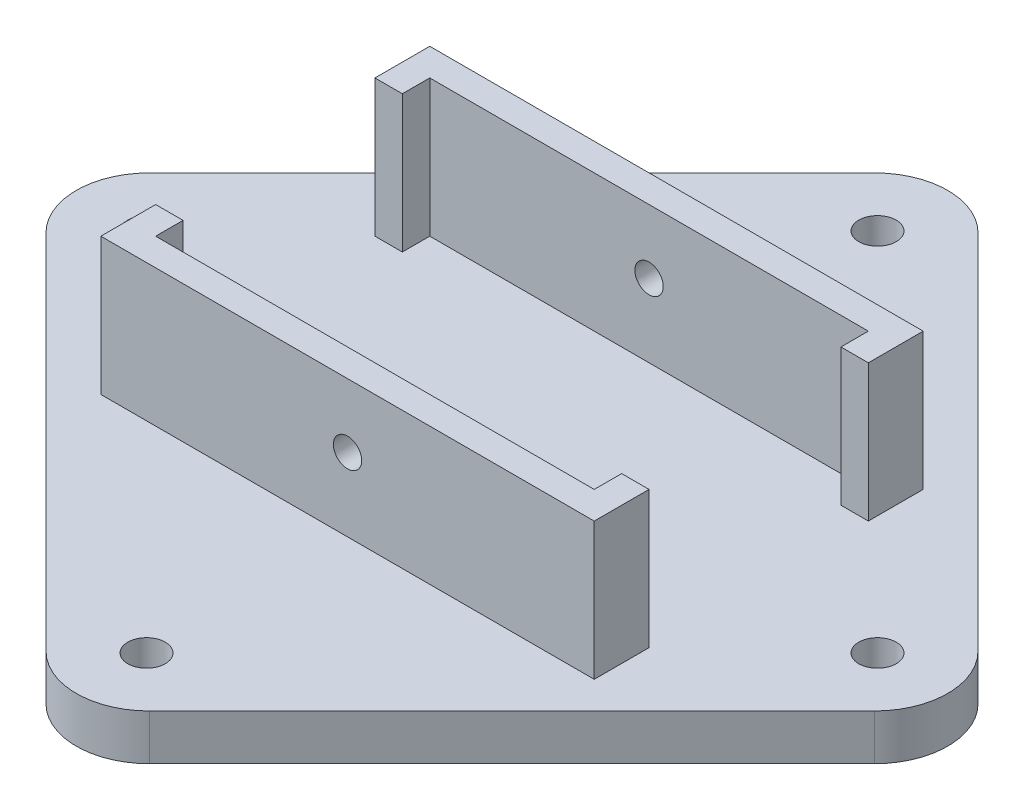
SolidWorks part; units mm, degrees
ref_plane "前视基准面" through (0, 0, 0) normal (0, 0, 1) x (1, 0, 0)
ref_plane "上视基准面" through (0, 0, 0) normal (0, 1, 0) x (1, 0, 0)
ref_plane "右视基准面" through (0, 0, 0) normal (1, 0, 0) x (0, 0, -1)
sketch "草图1" plane through (0, 0, 0) normal (0, 1, 0) x (1, 0, 0)
  line L1 (-5.6569, 45.3431) -> (-45.3431, 5.6569)
  line L2 (-45.3431, -5.6569) -> (-5.6569, -45.3431)
  line L3 (5.6569, -45.3431) -> (45.3431, -5.6569)
  line L4 (45.3431, 5.6569) -> (5.6569, 45.3431)
  circle A0 centre (0, 0) radius 36.0624 construction
  circle A1 centre (0, 40) radius 2.05
  circle A2 centre (40, 0) radius 2.05
  circle A3 centre (0, -40) radius 2.05
  circle A4 centre (-40, 0) radius 2.05
  arc A5 (-45.3431, 5.6569) -> (-45.3431, -5.6569) centre (-39.6863, 0) ccw
  arc A6 (-5.6569, -45.3431) -> (5.6569, -45.3431) centre (0, -39.6863) ccw
  arc A7 (45.3431, 5.6569) -> (45.3431, -5.6569) centre (39.6863, 0) cw
  arc A8 (5.6569, 45.3431) -> (-5.6569, 45.3431) centre (0, 39.6863) ccw
  point P18 (0, 0)
  point P25 (0, 51)
  dimension "D3" = 4.1
  dimension "D5" = 8
  dimension "D1" = 51
  dimension "D4" = 40
  dimension "D2" = 4
extrude "凸台-拉伸1" add sketch "草图1" along normal blind 5
sketch "草图2" plane through (0, 5, 0) normal (0, 1, 0) x (1, 0, 0)
  line L0 (-27, 12) -> (-24, 12)
  line L1 (27, -18) -> (-27, -18)
  line L2 (27, -18) -> (27, -12)
  line L3 (27, 18) -> (-27, 18)
  line L4 (-27, -18) -> (-27, -12)
  line L5 (27, -18) -> (-27, 18) construction
  line L6 (27, 18) -> (-27, -18) construction
  line L7 (24, -15) -> (-24, -15)
  line L8 (24, -15) -> (24, -12)
  line L9 (24, 15) -> (-24, 15)
  line L10 (-24, -15) -> (-24, -12)
  line L11 (24, -15) -> (-24, 15) construction
  line L12 (24, 15) -> (-24, -15) construction
  line L13 (0, 0) -> (-10.7692, 0) construction
  line L14 (0, 0) -> (0, 9.6792) construction
  line L15 (-27, -12) -> (-24, -12)
  line L16 (27, -12) -> (24, -12)
  line L17 (27, 12) -> (24, 12)
  line L18 (-24, 12) -> (-24, 15)
  line L19 (-27, 12) -> (-27, 18)
  line L20 (27, 12) -> (27, 18)
  line L21 (24, 12) -> (24, 15)
  point P0 (0, 0)
  point P6 (0, 0)
  dimension "D1" = 54
  dimension "D2" = 36
  dimension "D3" = 3
  dimension "D4" = 3
  dimension "D5" = 6
extrude "凸台-拉伸2" add sketch "草图2" along normal blind 15
sketch "草图3" plane through (0, 0, 18) normal (0, 0, 1) x (1, 0, 0)
  line L0 (-27, 5) -> (27, 5) construction
  line L1 (-5.6569, 0) -> (5.6569, 0) construction
  circle A0 centre (0, 13) radius 1.55
  point P4 (0, 0)
  point P5 (0, 0)
  dimension "D1" = 3.1
  dimension "D2" = 8
extrude "切除-拉伸1" cut sketch "草图3" against normal through all and the other way through all
